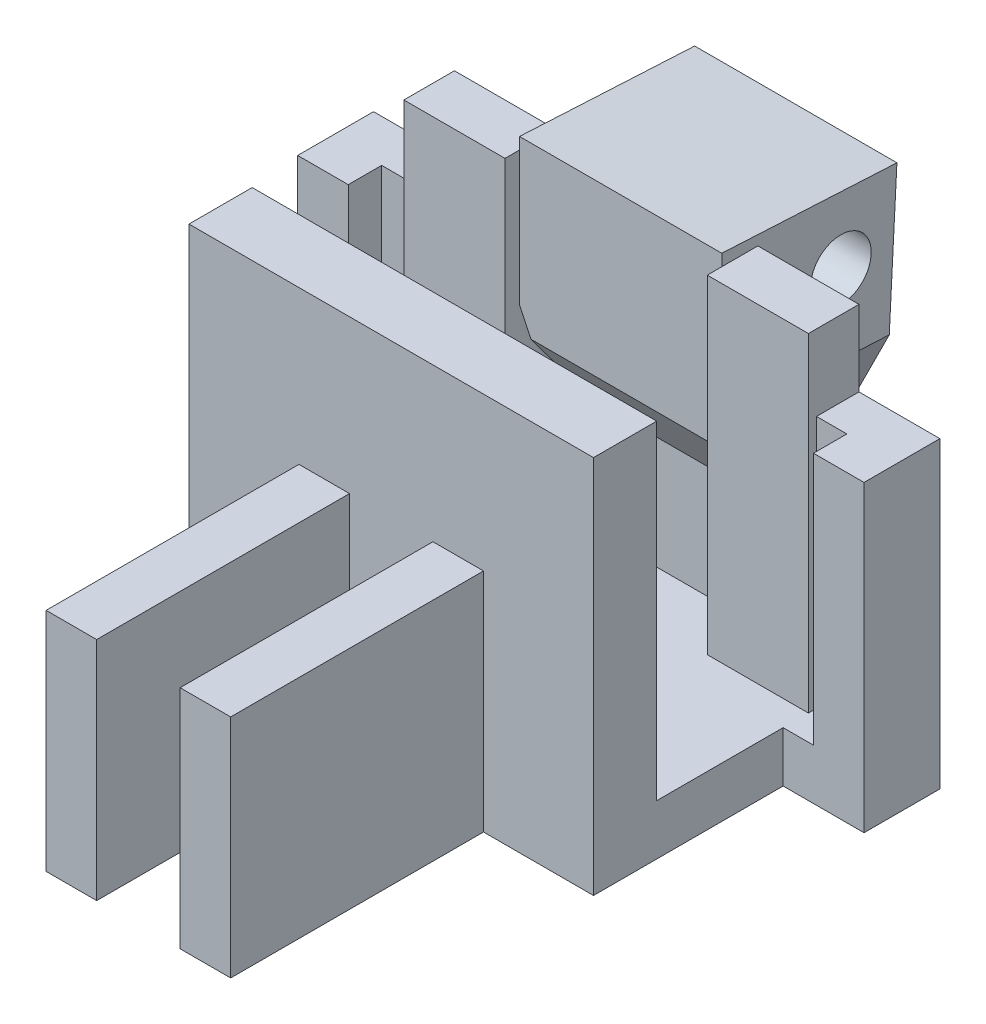
SolidWorks part; units mm, degrees
ref_plane "前视基准面" through (0, 0, 0) normal (0, 0, 1) x (1, 0, 0)
ref_plane "上视基准面" through (0, 0, 0) normal (0, 1, 0) x (1, 0, 0)
ref_plane "右视基准面" through (0, 0, 0) normal (1, 0, 0) x (0, 0, -1)
sketch "草图1" plane through (0, 0, 0) normal (0, 1, 0) x (1, 0, 0)
  line L1 (8, -5.25) -> (-8, -5.25)
  line L2 (8, -5.25) -> (8, 5.25)
  line L3 (8, 5.25) -> (-8, 5.25)
  line L4 (-8, -5.25) -> (-8, 5.25)
  line L5 (8, -5.25) -> (-8, 5.25) construction
  line L6 (8, 5.25) -> (-8, -5.25) construction
  line L7 (8, 5.25) -> (-8, 5.25)
  line L8 (8, 5.25) -> (8, 3.25)
  line L9 (8, 3.25) -> (-8, 3.25)
  line L10 (-8, 5.25) -> (-8, 3.25)
  line L11 (8, -5.25) -> (-8, -5.25)
  line L12 (8, -5.25) -> (8, -2.75)
  line L13 (8, -2.75) -> (-8, -2.75)
  line L14 (-8, -5.25) -> (-8, -2.75)
  point P0 (0, 0)
  dimension "D1" = 6
  dimension "D2" = 10.5
  dimension "D3" = 2
  dimension "D4" = 16
extrude "凸台-拉伸1" add sketch "草图1" along normal blind 2 contours L13 L2 L9 L4 region at (0, 0, -0.25)
extrude "凸台-拉伸2" add sketch "草图1<3>" along normal blind 15 contours L9 L2 L3 L4 | L2 L13 L4 L1 region at (0, 0, 4) region at (0, 0, -4.25)
sketch "草图1<3>" plane through (0, 0, 0) normal (0, 1, 0) x (1, 0, 0) same geometry as "草图1"
sketch "草图2" plane through (0, 0, -5.25) normal (0, 0, -1) x (-1, 0, 0)
  line L0 (0, 12.199) -> (0, -4.867) construction
  line L1 (-8, 15) -> (8, 15) construction
  line L2 (4, 28) -> (-4, 28)
  line L3 (4, 28) -> (4, 2)
  line L4 (4, 2) -> (-4, 2)
  line L5 (-4, 28) -> (-4, 2)
  line L6 (4, 28) -> (-4, 2) construction
  line L7 (4, 2) -> (-4, 28) construction
  line L8 (-8, 2) -> (8, 2) construction
  point P3 (0, 15)
  dimension "D1" = 8
  dimension "D2" = 0
extrude "切除-拉伸1" cut sketch "草图2" against normal up to surface (2 mm away) up to face at (0, 8.5, -3.25)
sketch "草图3" plane through (0, 0, 0) normal (1, 0, 0) x (0, 0, -1)
  line L0 (5.25, 0) -> (9.9537, 0)
  line L1 (9.9537, 0) -> (10.7506, 15.0981)
  line L2 (10.7506, 15.0981) -> (5.25, 15.3884)
  line L3 (5.25, 15.3884) -> (5.25, 0)
extrude "凸台-拉伸3" add sketch "草图3" along normal mid plane 5
sketch "草图4" plane through (8, 0, 0) normal (1, 0, 0) x (0, 0, -1)
  line L0 (3.25, 15) -> (3.25, 2) construction
  line L1 (5.25, 15) -> (3.25, 15)
  line L2 (5.25, 15) -> (5.25, 11.7656)
  line L3 (5.25, 11.7656) -> (3.25, 11.7656)
  line L4 (3.25, 15) -> (3.25, 11.7656)
sketch "草图5" plane through (2.5, 0, 0) normal (1, 0, 0) x (0, 0, -1)
  line L0 (5.25, 6.4511) -> (3.8228, 8.745)
  line L1 (5.25, 15) -> (5.25, 0) construction
  line L2 (3.8228, 8.745) -> (3.8228, 15.4638)
  line L3 (2.7617, 15.5198) -> (10.7506, 15.0981) construction
  line L4 (3.8228, 15.4638) -> (5.25, 15.3884)
  line L5 (5.25, 15.3884) -> (5.25, 6.4511)
extrude "凸台-拉伸4" add sketch "草图5" against normal up to surface (5 mm away) up to face at (-2.5, 6.4973, -7.2909)
sketch "草图6" plane through (-2.5, 0, 0) normal (-1, 0, 0) x (0, 0, 1)
  line L0 (-5.25, 6.4511) -> (-10.2802, 6.1856)
  line L7 (-5.25, 2) -> (-5.25, 6.4511)
  line L8 (-5.25, 6.4511) -> (-3.8228, 8.745)
  line L9 (-3.8228, 8.745) -> (-3.8228, 15.4638)
  line L10 (-3.8228, 15.4638) -> (-10.7506, 15.0981)
  line L11 (-10.7506, 15.0981) -> (-9.9537, 0)
  line L12 (-9.9537, 0) -> (-5.25, 0)
  line L13 (-5.25, 0) -> (-5.25, 2)
  line L15 (-5.25, 6.4511) -> (-3.8228, 8.745)
  line L16 (-3.8228, 8.745) -> (-3.8228, 15.4638)
  line L17 (-3.8228, 15.4638) -> (-10.7506, 15.0981)
  line L18 (-10.7506, 15.0981) -> (-10.2802, 6.1856)
  dimension "D1" = 0
extrude "凸台-拉伸5" add sketch "草图6" along normal up to surface (1.5 mm away) up to face at (-4, 8.5, -4.25)
sketch "草图7" plane through (0, -0.5239, -9.9261) normal (0, -0.0527, -0.9986) x (-1, 0, 0)
  line L0 (2.5, 6.7188) -> (4, 9.8921)
  line L1 (4, 15.6437) -> (4, 6.7188) construction
  line L2 (4, 9.8921) -> (4, 6.7188)
  line L3 (4, 6.7188) -> (2.5, 6.7188)
extrude "切除-拉伸3" cut sketch "草图7" against normal up to surface (6.4664 mm away) up to face at (-1.4, 12.6835, -3.8228)
mirror "镜向2" about plane through (0, 0, 0) normal (1, 0, 0) of "切除-拉伸3", "凸台-拉伸5"
sketch "草图8" plane through (4, 0, 0) normal (1, 0, 0) x (0, 0, -1)
  circle A0 centre (8.5337, 12.5417) radius 1.2
extrude "切除-拉伸4" cut sketch "草图8" against normal up to surface (8 mm away) up to face at (-4, 13.2575, -6.5573)
sketch "草图9" plane through (0, 0, 0) normal (0, -1, 0) x (1, 0, 0)
  line L0 (8, -5.25) -> (11.2, -5.25)
  line L1 (11.2, -5.25) -> (11.2, -2.25)
  line L2 (11.2, -2.25) -> (9.2, -2.25)
  line L4 (8, -3.5704) -> (8, -5.25)
  line L5 (9.2, -2.25) -> (9.2, -3.5704)
  line L6 (9.2, -3.5704) -> (8, -3.5704)
  line L7 (9.2, -2.25) -> (8, -2.25)
  line L8 (8, 5.25) -> (8, -5.25) construction
  line L9 (8, -2.25) -> (8, -3.5704)
  line L10 (0, 0) -> (0, -12.5877) construction
  line L11 (-8, -2.25) -> (-8, -3.5704)
  line L12 (-9.2, -2.25) -> (-8, -2.25)
  line L13 (-9.2, -3.5704) -> (-8, -3.5704)
  line L14 (-9.2, -2.25) -> (-9.2, -3.5704)
  line L15 (-8, -3.5704) -> (-8, -5.25)
  line L16 (-11.2, -2.25) -> (-9.2, -2.25)
  line L17 (-11.2, -5.25) -> (-11.2, -2.25)
  line L18 (-8, -5.25) -> (-11.2, -5.25)
  line M7 (8, -5.25) -> (8, 5.25)
  line M9 (-8, 5.25) -> (-8, -5.25)
  dimension "D1" = 3
  dimension "D2" = 1.2
  dimension "D3" = 2
extrude "凸台-拉伸6" add sketch "草图9" against normal up to surface (2 mm away) contours L5 L7 L6 M7 | L12 L14 L13 M9 region at (8.6, 0, -2.9102) region at (-8.6, 0, -2.9102) up to face at (0, 2, -2.85)
extrude "凸台-拉伸7" add sketch "草图9<3>" against normal blind 12 contours L5 L6 L0 L1 L2 M7 | L18 L13 L14 L16 L17 M9 region at (9.7977, 0, -3.916) region at (-9.7977, 0, -3.916)
sketch "草图9<3>" plane through (0, 0, 0) normal (0, -1, 0) x (1, 0, 0) same geometry as "草图9"
sketch "草图10" plane through (0, 0, 5.25) normal (0, 0, 1) x (1, 0, 0)
  line L0 (0, -1.5666) -> (0, 16.0986) construction
  line L1 (8, 0) -> (-8, 0) construction
  line L2 (1.65, 0) -> (3.65, 0)
  line L3 (1.65, 0) -> (1.65, 8.9431)
  line L4 (1.65, 8.9431) -> (3.65, 8.9431)
  line L5 (3.65, 0) -> (3.65, 8.9431)
  line L6 (-3.65, 0) -> (-3.65, 8.9431)
  line L7 (-1.65, 8.9431) -> (-3.65, 8.9431)
  line L8 (-1.65, 0) -> (-1.65, 8.9431)
  line L9 (-1.65, 0) -> (-3.65, 0)
  dimension "D1" = 1.65
  dimension "D2" = 2
extrude "凸台-拉伸8" add sketch "草图10" along normal blind 10
